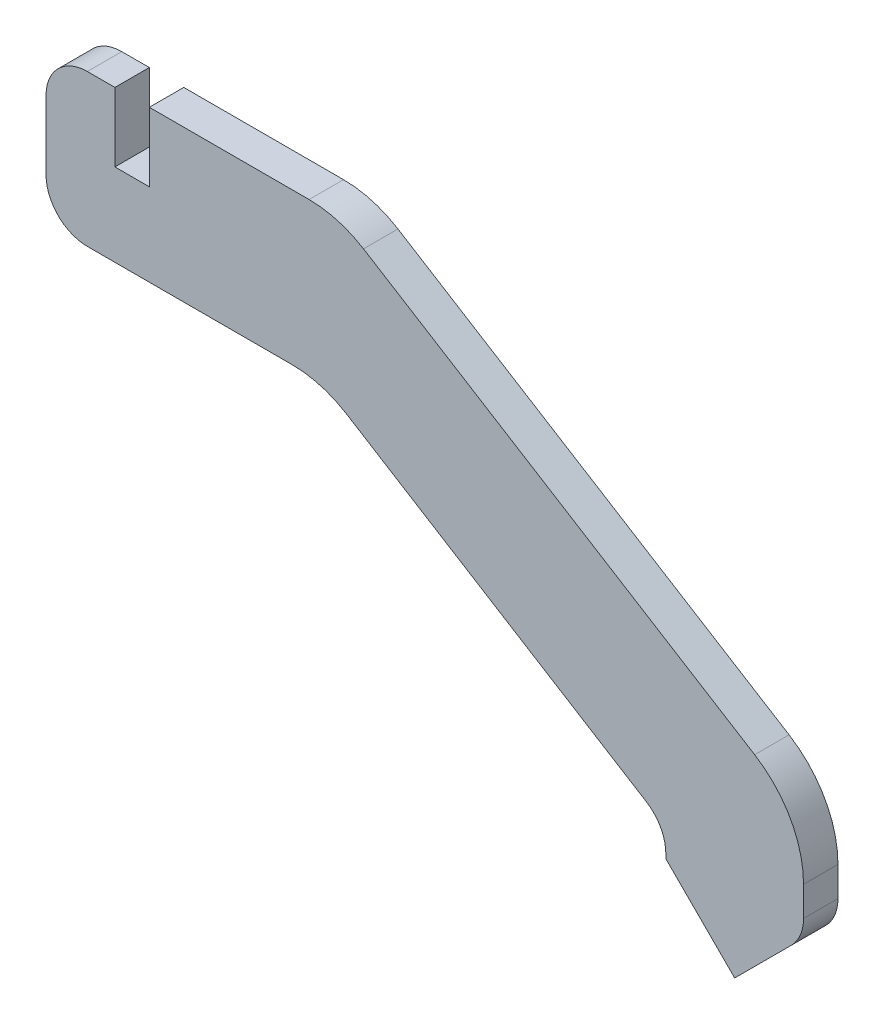
SolidWorks part; units mm, degrees
material "PBT General Purpose"
ref_plane "Front Plane" through (0, 0, 0) normal (0, 0, 1) x (1, 0, 0)
ref_plane "Top Plane" through (0, 0, 0) normal (0, 1, 0) x (1, 0, 0)
ref_plane "Right Plane" through (0, 0, 0) normal (1, 0, 0) x (0, 0, -1)
sketch "frame_outline" plane through (0, 0, 0) normal (0, 0, 1) x (1, 0, 0)
  line L127 (0, 0) -> (0, 1.1)
  line L128 (0, 1.1) -> (0.5, 1.1)
  line L129 (0.5, 1.1) -> (0.5, 0.6)
  line L130 (0.5, 0.6) -> (0.75, 0.6)
  line L131 (0.75, 0.6) -> (0.75, 1.1)
  line L132 (0.75, 1.1) -> (2.1236, 1.1)
  line L133 (2.1236, 1.1) -> (5.5, -0.9934)
  line L134 (5.5, -0.9934) -> (5.5, -1.75)
  line L135 (5.5, -1.75) -> (5, -2.25)
  line L136 (5, -2.25) -> (4.5, -1.75)
  line L137 (4.5, -1.75) -> (4.5, -1.55)
  line L138 (4.5, -1.55) -> (2, 0)
  line L139 (2, 0) -> (0, 0)
  dimension "D1" = 0.25
  dimension "D2" = 0.5
  dimension "D3" = 0.6
  dimension "D4" = 0.5
  dimension "D5" = 5
  dimension "D6" = 2.25
  dimension "D7" = 1
  dimension "D8" = 1
  dimension "D9" = 0.2
  dimension "D10" = 2
extrude "Boss-Extrude1" add sketch "frame_outline" along normal mid plane 0.25
fillet "Fillet1" radius 0.3 4 edges at (5.5, -1.75, 0) (0, 1.1, 0) (4.5, -1.55, 0) (0, 0, 0)
fillet "Fillet2" radius 0.75 3 edges at (5.5, -0.9934, 0) (2.1236, 1.1, 0) (2, 0, 0)
equation "\"t\"= 0.25'thickness of the sheets"
equation "\"t_cf\" = 0.115'thickness of single carbon fiber layer"
equation "\"t_kapton\" = 0.025'thickness of single Kapton flex layer"
equation "\"t_fr4\" = 0.1'thickness of FR4 with copper layer"
equation "\"joint_flex\"= 0.1'Width of flextures gap"
equation "\"joint_flex_eff\"= 0.02'Width of flecture after castelation"
equation "\"joint_fold\"= 0.2'Width of folding joints for 90deg fold"
equation "\"gap_tolerance\"= 0.002'Width to have interfecence fit between carbon fiber inserts"
equation "\"assemble_angle\"= 90'Angle of assembly parts"
equation "\"D1@Boss-Extrude1\"=\"t\""
equation "\"link_lift\"= 0.5'Actuation linkage amplification for the lift motion"
equation "\"link_swing\"= 0.45'Actuation linkage amplification for the swing motion"
equation "\"D1@frame_outline\"=\"t\""
